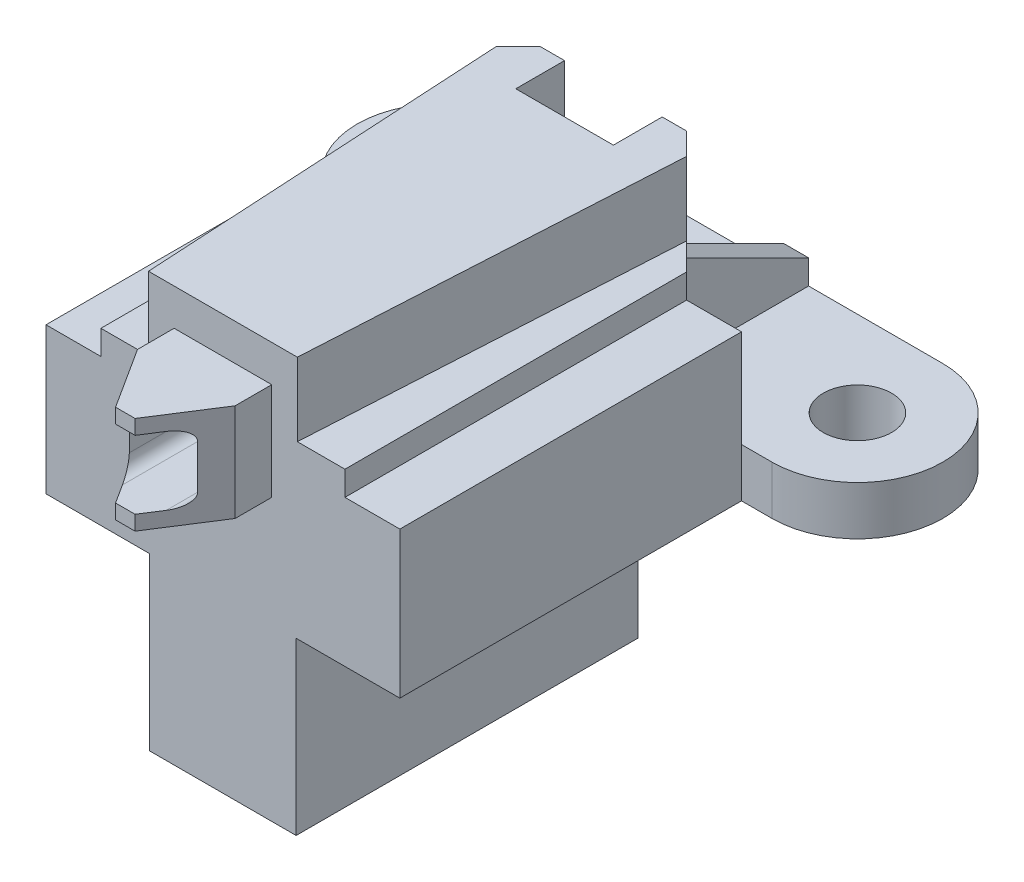
SolidWorks part; units mm, degrees
material "Nylon 101"
ref_plane "Płaszczyzna przednia" through (0, 0, 0) normal (0, 0, 1) x (1, 0, 0)
ref_plane "Płaszczyzna górna" through (0, 0, 0) normal (0, 1, 0) x (1, 0, 0)
ref_plane "Płaszczyzna prawa" through (0, 0, 0) normal (1, 0, 0) x (0, 0, -1)
sketch "Szkic1" plane through (0, 0, 0) normal (0, 1, 0) x (1, 0, 0)
  line L0 (0, 0) -> (-17, 0) construction
  line L1 (-8.5, 0) -> (-8.5, -17.5) construction
  line L2 (-15.75, -3.5) -> (-15.75, -17.5)
  line L3 (-1.25, -3.5) -> (-1.25, -17.5)
  line L4 (-11.5, -3.5) -> (-11.5, -17.5)
  line L5 (-5.5, -3.5) -> (-5.5, -17.5)
  line L6 (-17, 0) -> (0, 0) construction
  line L7 (-17, 3.5) -> (0, 3.5)
  line L8 (-17, -3.5) -> (0, -3.5)
  line L9 (-11.5, 3.5) -> (-11.5, -3.5)
  line L10 (-5.5, 3.5) -> (-5.5, -3.5)
  line L11 (-11.5, -17.5) -> (-5.5, -17.5)
  line L12 (-10.5, 3.5) -> (-10.5, -3.5)
  line L13 (-11.5, 0) -> (-11.5, -17.5) construction
  line L14 (-5.5, 0) -> (-5.5, -17.5) construction
  line L15 (-15.75, 0) -> (-15.75, -17.5) construction
  line L16 (-1.25, 0) -> (-1.25, -17.5) construction
  line L17 (-6.5, 3.5) -> (-6.5, -3.5)
  line L18 (-15.75, -17.5) -> (-11.5, -17.5)
  line L19 (-5.5, -17.5) -> (-1.25, -17.5)
  circle A0 centre (-17, 0) radius 1.4
  circle A1 centre (0, 0) radius 1.4
  arc A2 (-17, 3.5) -> (-17, -3.5) centre (-17, 0) ccw
  arc A3 (0, -3.5) -> (0, 3.5) centre (0, 0) ccw
  point P16 (-8.5, 0)
  dimension "D2" = 2.8
  dimension "D1" = 17
  dimension "D7" = 7
  dimension "D8" = 6
  dimension "D9" = 21
  dimension "D10" = 1
  dimension "D3" = 7.25
  dimension "D4" = 7.25
  dimension "D5" = 3
  dimension "D6" = 3
  dimension "D11" = 1
extrude "Dodanie-wyciągnięcie1" add sketch "Szkic1" along normal blind 2 contours A1 | A0 | L7 A3 L8 A2 region at (-17, 0, 0) region at (0, 0, 0)
extrude "Dodanie-wyciągnięcie2" add sketch "Szkic1<3>" along normal blind 7 contours L2 L18 L4 L8 | L4 L11 L5 L8 | L5 L19 L3 L8 region at (-13.625, 0, 10.5) region at (-8.5, 0, 10.5) region at (-3.375, 0, 10.5)
sketch "Szkic1<3>" plane through (0, 0, 0) normal (0, 1, 0) x (1, 0, 0) same geometry as "Szkic1"
extrude "Dodanie-wyciągnięcie3" add sketch "Szkic1<4>" against normal blind 7 contours L4 L11 L5 L8 region at (-8.5, 0, 10.5)
sketch "Szkic1<4>" plane through (0, 0, 0) normal (0, 1, 0) x (1, 0, 0) same geometry as "Szkic1"
sketch "Szkic2" plane through (0, 7, 0) normal (0, 1, 0) x (1, 0, 0)
  line L0 (-8.5, -3.5) -> (-8.5, -17.5) construction
  line L1 (-15.75, -3.5) -> (-1.25, -3.5) construction
  line L2 (-15.75, -17.5) -> (-1.25, -17.5) construction
  line L3 (-13.5, -3.5) -> (-13.5, -17.5)
  line L4 (-3.5, -3.5) -> (-3.5, -17.5)
  line L5 (-13.5, -17.5) -> (-3.5, -17.5)
  line L6 (-13.5, -3.5) -> (-3.5, -3.5)
  dimension "D1" = 5
  dimension "D2" = 5
extrude "Dodanie-wyciągnięcie4" add sketch "Szkic2" along normal blind 3
extrude "Dodanie-wyciągnięcie5" add sketch "Szkic1<5>" along normal blind 3.5 from surface contours L7 L17 L8 L10 | L12 L7 L9 L8 region at (-11, 0, 0) region at (-6, 0, 0) starting at face at (0, 2, 1.4)
sketch "Szkic1<5>" plane through (0, 0, 0) normal (0, 1, 0) x (1, 0, 0) same geometry as "Szkic1"
sketch "Szkic3" plane through (0, 2, 0) normal (0, 1, 0) x (1, 0, 0)
  line L1 (-3.5, -3.5) -> (-1.25, -3.5) construction
  line L2 (-10.5, -3.5) -> (-10.5, 3.5) construction
  line L3 (-3.5, -3.5) -> (-1.25, -3.5) construction
  line L4 (-3.5, -3.5) -> (-5.5, -1.5)
  line L5 (-5.5, -3.5) -> (-5.5, 3.5) construction
  line L7 (-5.5, -3.5) -> (-3.5, -3.5)
  line L8 (-8.5, -3.5) -> (-8.5, 3.5) construction
  line L9 (-10.5, -3.5) -> (-6.5, -3.5) construction
  line L10 (-10.5, 3.5) -> (-6.5, 3.5) construction
  line L12 (-11.5, -3.5) -> (-13.5, -3.5)
  line L13 (-13.5, -3.5) -> (-11.5, -1.5)
  line L14 (-6.5, -3.5) -> (-6.5, 3.5) construction
  line L15 (-10.5, -3.5) -> (-10.5, -1.5)
  line L16 (-6.5, -3.5) -> (-6.5, -1.5)
  line L17 (-5.5, -1.5) -> (-6.5, -1.5)
  line L18 (-5.5, -3.5) -> (-6.5, -3.5)
  line L19 (-10.5, -3.5) -> (-11.5, -3.5)
  line L20 (-11.5, -1.5) -> (-10.5, -1.5)
  dimension "D1" = 2
extrude "Dodanie-wyciągnięcie6" add sketch "Szkic3" along normal up to surface (8 mm away) up to face at (-8.5, 10, 10.5)
sketch "Szkic4" plane through (-11.5, 0, 0) normal (-1, 0, 0) x (0, 0, 1)
  line L0 (1.5, 5.5) -> (-3.5, 3)
  line L1 (-3.5, 5.5) -> (-3.5, 2) construction
  line L2 (-3.5, 3) -> (-3.5, 5.5)
  line L3 (-3.5, 5.5) -> (1.5, 5.5)
  dimension "D1" = 1
extrude "Wytnij-wyciągnięcie1" cut sketch "Szkic4" against normal up to surface (6 mm away) up to face at (-5.5, 3.75, -1)
sketch "Szkic5" plane through (0, 10, 0) normal (0, 1, 0) x (1, 0, 0)
  line L0 (-8.5, -17.5) -> (-8.5, -1.5) construction
  line L1 (-13.5, -17.5) -> (-3.5, -17.5) construction
  line L2 (-8.5, -17.5) -> (-5.45, -17.5) construction
  line L3 (-5.45, -17.5) -> (-4.55, -1.5) construction
  line L4 (-5.45, -17.5) -> (-3.5, -17.5)
  line L5 (-3.5, -17.5) -> (-3.5, -3.5)
  line L6 (-3.5, -3.5) -> (-4.6006, -2.3994)
  line L7 (-5.5, -1.5) -> (-3.5, -3.5) construction
  line L8 (-5.45, -17.5) -> (-4.6006, -2.3994)
  line L9 (-13.5, -3.5) -> (-12.3994, -2.3994)
  line L10 (-13.5, -17.5) -> (-13.5, -3.5)
  line L11 (-11.55, -17.5) -> (-12.3994, -2.3994)
  line L12 (-11.55, -17.5) -> (-13.5, -17.5)
  dimension "D1" = 3.05
  dimension "D2" = 3.95
extrude "Wytnij-wyciągnięcie2" cut sketch "Szkic5" against normal up to surface (3 mm away) up to face at (-14.625, 7, 10.5)
sketch "Szkic6" plane through (0, 7, 0) normal (0, 1, 0) x (1, 0, 0)
  line L0 (-11.55, -17.5) -> (-5.45, -17.5) construction
  line L1 (-11.55, -17.5) -> (-5.45, -17.5) construction
  line L2 (-8.5, -17.5) -> (-3.5, -17.5) construction
  line L3 (-5.45, -17.5) -> (-1.25, -17.5) construction
  line L4 (-3.5, -17.5) -> (-3.5, -3.5)
  line L5 (-3.5, -3.5) -> (-1.25, -3.5)
  line L6 (-1.25, -3.5) -> (-1.25, -17.5)
  line L7 (-8.5, -17.5) -> (-8.5, -7.2826) construction
  line L8 (-1.25, -17.5) -> (-3.5, -17.5)
  line L9 (-15.75, -17.5) -> (-13.5, -17.5)
  line L10 (-15.75, -3.5) -> (-15.75, -17.5)
  line L11 (-13.5, -3.5) -> (-15.75, -3.5)
  line L12 (-13.5, -17.5) -> (-13.5, -3.5)
extrude "Wytnij-wyciągnięcie3" cut sketch "Szkic6" against normal blind 1
sketch "Szkic7" plane through (0, 0, 17.5) normal (0, 0, 1) x (1, 0, 0)
  line L0 (-8.5, 10) -> (-8.5, -7) construction
  line L1 (-11.55, 10) -> (-5.45, 10) construction
  line L2 (-11.5, -7) -> (-5.5, -7) construction
  line L3 (-10.5, 8.5) -> (-6.5, 8.5)
  line L4 (-6.5, 8.5) -> (-6.5, 4.5)
  line L5 (-6.5, 4.5) -> (-10.5, 4.5)
  line L6 (-10.5, 8.5) -> (-10.5, 4.5)
  point P11 (-8.5, 8.5)
  point P12 (-8.5, 4.5)
  dimension "D1" = 2
  dimension "D2" = 1.5
  dimension "D3" = 4
extrude "Dodanie-wyciągnięcie7" add sketch "Szkic7" along normal blind 4
sketch "Szkic8" plane through (0, 8.5, 0) normal (0, 1, 0) x (1, 0, 0)
  line L1 (-6.5, -21.5) -> (-10.5, -21.5) construction
  line L4 (-8.1, -21.5) -> (-6.5, -19)
  line L5 (-6.5, -21.5) -> (-6.5, -17.5) construction
  line L6 (-8.1, -21.5) -> (-6.5, -21.5)
  line L8 (-8.9, -21.5) -> (-10.5, -19)
  line L14 (-6.5, -17.5) -> (-10.5, -17.5)
  line L15 (-10.5, -17.5) -> (-10.5, -21.5)
  line L16 (-10.5, -21.5) -> (-6.5, -21.5)
  line L17 (-6.5, -21.5) -> (-6.5, -17.5)
  line L19 (-10.5, -19) -> (-10.5, -21.5)
  line L20 (-10.5, -21.5) -> (-8.9, -21.5)
  line L21 (-6.5, -21.5) -> (-6.5, -19)
  dimension "D1" = 0
extrude "Wytnij-wyciągnięcie4" cut sketch "Szkic8" against normal up to surface (4 mm away) up to face at (-8.5, 4.5, 19.5)
sketch "Szkic9" plane through (0, 0, 21.5) normal (0, 0, 1) x (1, 0, 0)
  line L0 (-8.5, 4.5) -> (-8.5, 8.5) construction
  line L1 (-8.9, 4.5) -> (-8.1, 4.5) construction
  line L2 (-8.1, 8.5) -> (-8.9, 8.5) construction
  line L3 (-10.5, 4.5) -> (-10.5, 8.5) construction
  line L4 (-7.6, 7.9) -> (-9.4, 7.9)
  line L5 (-7.1, 7.4) -> (-7.1, 5.6)
  line L6 (-7.6, 5.1) -> (-9.4, 5.1)
  line L7 (-9.9, 7.4) -> (-9.9, 5.6)
  line L8 (-7.1, 7.9) -> (-9.9, 5.1) construction
  line L9 (-7.1, 5.1) -> (-9.9, 7.9) construction
  arc A0 (-9.4, 5.1) -> (-9.9, 5.6) centre (-9.4, 5.6) cw
  arc A1 (-9.4, 7.9) -> (-9.9, 7.4) centre (-9.4, 7.4) ccw
  arc A2 (-7.6, 7.9) -> (-7.1, 7.4) centre (-7.6, 7.4) cw
  arc A3 (-7.1, 5.6) -> (-7.6, 5.1) centre (-7.6, 5.6) cw
  point P6 (-8.5, 6.5)
  dimension "D1" = 0.6
  dimension "D2" = 0.5
extrude "Wytnij-wyciągnięcie5" cut sketch "Szkic9" against normal through all
